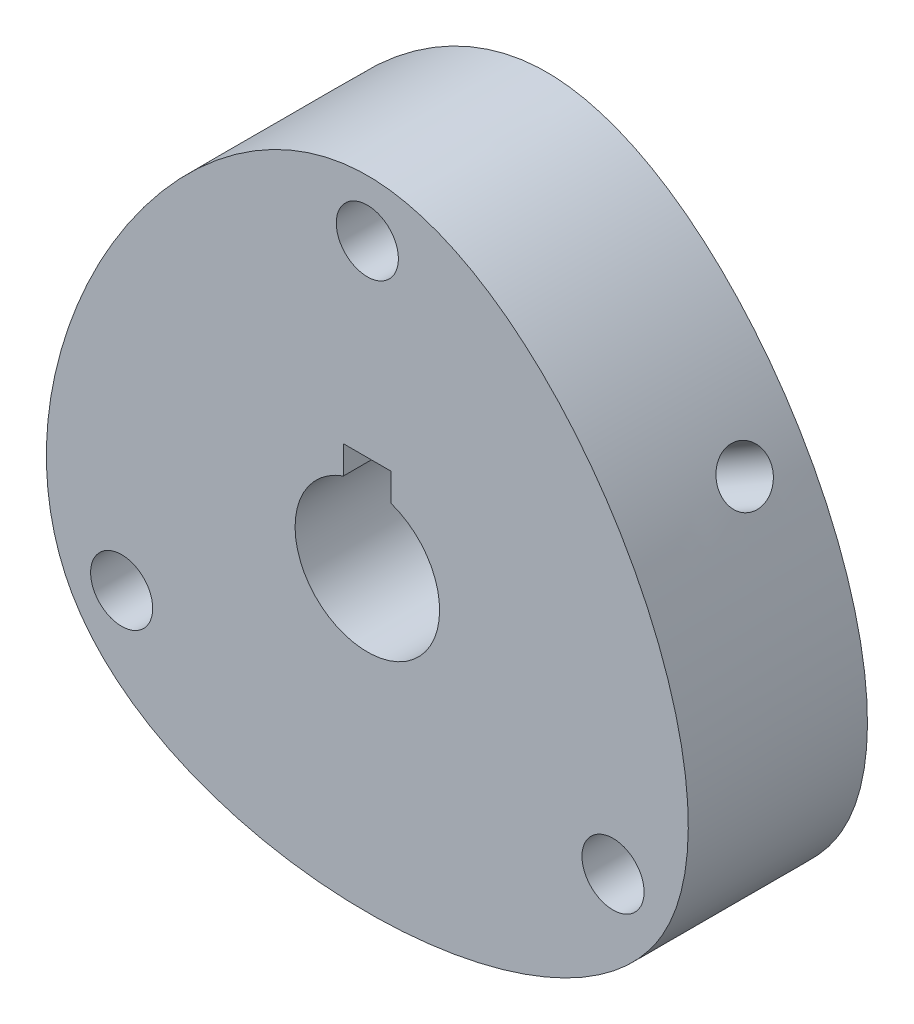
SolidWorks part; units mm, degrees
ref_plane "正面" through (0, 0, 0) normal (0, 0, 1) x (1, 0, 0)
ref_plane "平面" through (0, 0, 0) normal (0, 1, 0) x (1, 0, 0)
ref_plane "右側面" through (0, 0, 0) normal (1, 0, 0) x (0, 0, -1)
sketch "ｽｹｯﾁ1" plane through (0, 0, 0) normal (0, 0, 1) x (1, 0, 0)
  line L0 (0, 0) -> (-20.5681, -11.875) construction
  line L1 (0, 23.75) -> (-20.5681, -11.875) construction
  line L2 (-20.5681, -11.875) -> (20.5681, -11.875) construction
  line L3 (20.5681, -11.875) -> (0, 23.75) construction
  line L14 (-2, 4.05) -> (2, 4.05)
  line L15 (-2, 4.05) -> (-2, 8.05)
  line L16 (-2, 8.05) -> (2, 8.05)
  line L17 (2, 4.05) -> (2, 8.05)
  line L18 (-2, 4.05) -> (2, 8.05) construction
  line L19 (-2, 8.05) -> (2, 4.05) construction
  circle A0 centre (0, 0) radius 11.875 construction
  circle A1 centre (0, 23.75) radius 2.6
  circle A2 centre (20.5681, -11.875) radius 2.6
  circle A3 centre (-20.5681, -11.875) radius 2.6
  circle A4 centre (0, 0) radius 6.05
  circle A5 centre (0, 0) radius 28.5 construction
  ellipse E0 centre (20.5681, -11.875) end of major axis (23.0681, -7.5449) minor radius 4.75
  ellipse E1 centre (-20.5681, -11.875) end of major axis (-18.0681, -16.2051) minor radius 4.75
  ellipse E2 centre (0, 23.75) end of major axis (5, 23.75) minor radius 4.75
  spline S1 degree 3 poles (-49.3634, -28.5) (49.3634, -28.5) (0, 57) (-49.3634, -28.5) (49.3634, -28.5) (0, 57) knots -1 -0.666667 -0.333333 0 0.333333 0.666667 1 1.333333 1.666667 2 only from (24.6817, -14.25) to (24.6817, -14.25)
  point P26 (0, -5.7735)
  point P31 (0, 6.05)
  dimension "D1" = 5.2
  dimension "D2" = 5.2
  dimension "D3" = 5.2
  dimension "D5" = 12.1
  dimension "D6" = 57
  dimension "D4" = 23.75
  dimension "D8" = 4
  dimension "D9" = 4
extrude "ﾎﾞｽ - 押し出し1" add sketch "ｽｹｯﾁ1" along normal blind 15 contours E0 S1 E2 E1 A4 L15 L16 L17 | E0 A2 | E2 A1 | E1 A3 region at (-19.4081, -7.2836, 0) region at (3.3962, 27.0503, 0) region at (0, -24.1796, 0) region at (25.1244, -10.5839, 0)
sketch "ｽｹｯﾁ13" plane through (0, 0, 0) normal (0, 1, 0) x (1, 0, 0)
  line L0 (26.8701, 0) -> (-26.8701, 0) construction
  circle A0 centre (0, -5) radius 2.15
  dimension "D1" = 5
  dimension "D2" = 4.3
extrude "ｶｯﾄ - 押し出し10" cut sketch "ｽｹｯﾁ13" against normal through all
ref_axis "軸1" through (0, 0, 0) along (0, 0, 1)
ref_plane "平面1" through (0, 0, 0) normal (-0.866, -0.5, 0) x (0, 0, 1)
sketch "ｽｹｯﾁ14" plane through (0, 0, 0) normal (-0.866, -0.5, 0) x (0, 0, 1)
  line L0 (0, 26.8701) -> (0, -26.8701) construction
  circle A0 centre (5, 0) radius 2.15
  dimension "D1" = 5
  dimension "D2" = 4.3
extrude "ｶｯﾄ - 押し出し11" cut sketch "ｽｹｯﾁ14" against normal through all
sketch "ｽｹｯﾁ15" plane through (0, 0, 0) normal (0, 0, -1) x (-1, 0, 0)
  circle A0 centre (-20.5681, -11.875) radius 4.6
  circle A1 centre (0, 23.75) radius 4.6
  circle A2 centre (20.5681, -11.875) radius 4.6
  dimension "D1" = 9.2
  dimension "D2" = 9.2
  dimension "D3" = 9.2
extrude "ｶｯﾄ - 押し出し12" cut sketch "ｽｹｯﾁ15" against normal blind 5.2
